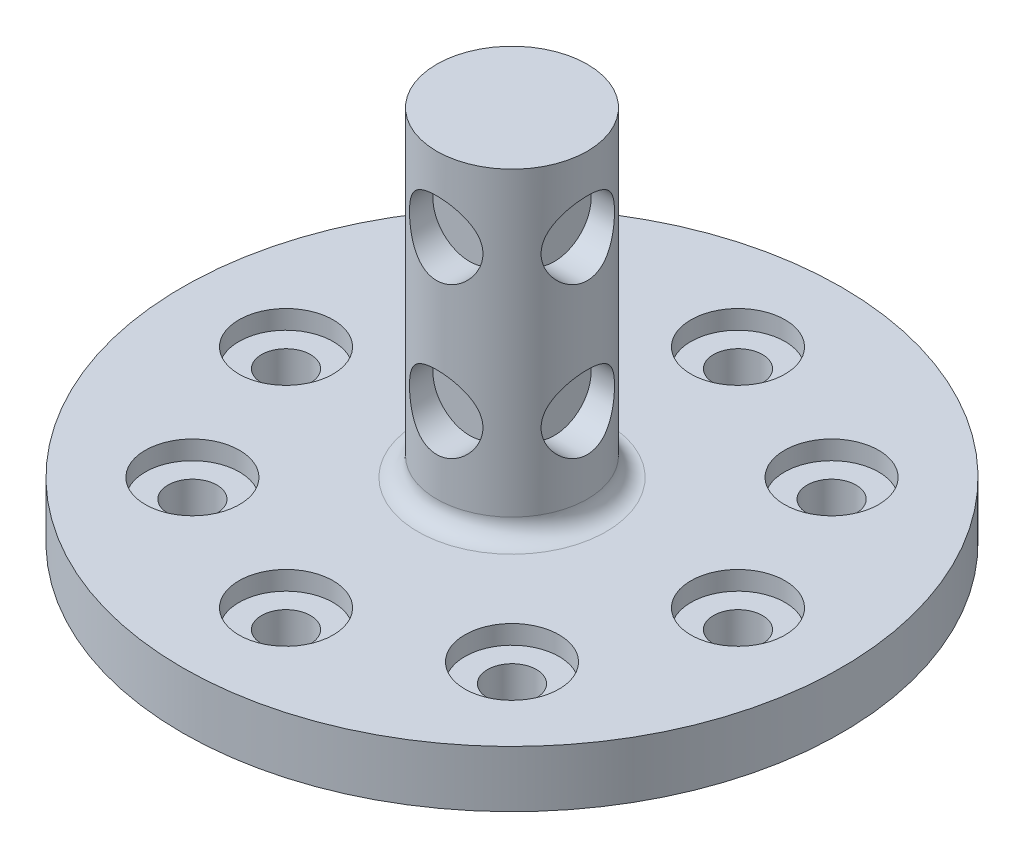
SolidWorks part; units mm, degrees
ref_plane "前视基准面" through (0, 0, 0) normal (0, 0, 1) x (1, 0, 0)
ref_plane "上视基准面" through (0, 0, 0) normal (0, 1, 0) x (1, 0, 0)
ref_plane "右视基准面" through (0, 0, 0) normal (1, 0, 0) x (0, 0, -1)
sketch "草图1" plane through (0, 0, 0) normal (0, 1, 0) x (1, 0, 0)
  circle A0 centre (0, 0) radius 4
  dimension "D1" = 8
extrude "凸台-拉伸1" add sketch "草图1" along normal blind 16
sketch "草图2" plane through (0, 0, 0) normal (0, 0, 1) x (1, 0, 0)
  line L0 (4, 0) -> (4, 16) construction
  line L1 (-4, 0) -> (4, 0) construction
  line L2 (4, 16) -> (-4, 16) construction
  line L3 (-4, 16) -> (-4, 0) construction
  line L4 (4, 0) -> (4, 16)
  line L5 (-4, 0) -> (4, 0)
  line L6 (4, 16) -> (-4, 16)
  line L7 (-4, 16) -> (-4, 0)
  circle A0 centre (0, 12) radius 1.95
  circle A1 centre (0, 4) radius 1.95
  point P3 (0, 12)
  point P5 (0, 4)
  dimension "D5" = 3.9
  dimension "D6" = 3.9
  dimension "D1" = 4
  dimension "D2" = 4
  dimension "D3" = 4
  dimension "D4" = 4
extrude "切除-拉伸1" cut sketch "草图2" against normal through all and the other way through all contours A1 | A0
pattern_circular "阵列(圆周)1" count 4 over 360 about axis through (0, 16, 0) along (0, 1, 0) of "切除-拉伸1"
sketch "草图3" plane through (0, 16, 0) normal (0, 1, 0) x (1, 0, 0)
  line L1 (-2.25, -2.25) -> (2.25, -2.25)
  line L2 (-2.25, -2.25) -> (-2.25, 2.25)
  line L3 (-2.25, 2.25) -> (2.25, 2.25)
  line L4 (2.25, -2.25) -> (2.25, 2.25)
  line L5 (-2.25, -2.25) -> (2.25, 2.25) construction
  line L6 (-2.25, 2.25) -> (2.25, -2.25) construction
  point P0 (0, 0)
  dimension "D1" = 4.5
  dimension "D2" = 4.5
extrude "凸台-拉伸3" add sketch "草图3" against normal up to surface (16 mm away) separate body up to face at (0, 0, 4)
sketch "草图5" plane through (0, 0, 0) normal (0, -1, 0) x (1, 0, 0)
  circle A1 centre (0, 0) radius 4
  circle A2 centre (0, 0) radius 4
  dimension "D1" = 0
extrude "凸台-拉伸5" add sketch "草图5" along normal blind 1
sketch "草图6" plane through (0, -1, 0) normal (0, -1, 0) x (1, 0, 0)
  circle A0 centre (0, 0) radius 17.5
  dimension "D1" = 35
extrude "凸台-拉伸6" add sketch "草图6" along normal blind 3
sketch "草图7" plane through (0, -4, 0) normal (0, -1, 0) x (1, 0, 0)
  circle A0 centre (0, 0) radius 7.5
  dimension "D1" = 15
extrude "切除-拉伸2" cut sketch "草图7" against normal blind 1.8
fillet "圆角1" radius 1 1 edges at (0, -1, -4)
sketch "草图8" plane through (0, -1, 0) normal (0, 1, 0) x (1, 0, 0)
  circle A0 centre (0, 0) radius 12 construction
  circle A1 centre (-12, 0) radius 1.3
  dimension "D1" = 24
  dimension "D2" = 2.6
extrude "切除-拉伸3" cut sketch "草图8" against normal through all
sketch "草图9" plane through (0, -1, 0) normal (0, 1, 0) x (1, 0, 0)
  circle A0 centre (-12, 0) radius 1.3 construction
  circle A1 centre (-12, 0) radius 1.3
  circle A2 centre (-12, 0) radius 2.5
  dimension "D1" = 5
extrude "切除-拉伸4" cut sketch "草图9" against normal blind 1
pattern_circular "阵列(圆周)2" count 8 over 360 about axis through (0, 16, 0) along (0, 1, 0) of "切除-拉伸3", "切除-拉伸4"
